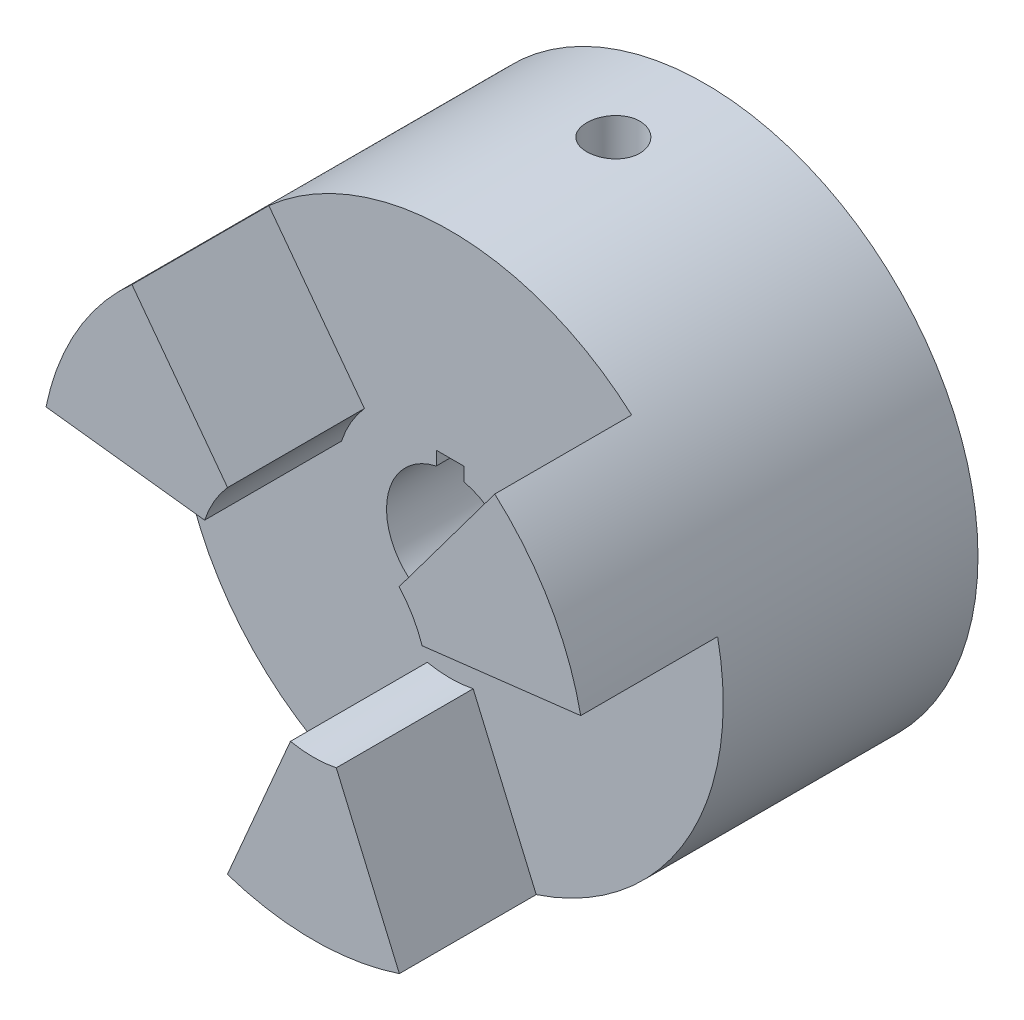
SolidWorks part; units mm, degrees
ref_plane "Płaszczyzna przednia" through (0, 0, 0) normal (0, 0, 1) x (1, 0, 0)
ref_plane "Płaszczyzna górna" through (0, 0, 0) normal (0, 1, 0) x (1, 0, 0)
ref_plane "Płaszczyzna prawa" through (0, 0, 0) normal (1, 0, 0) x (0, 0, -1)
sketch "Szkic1" plane through (0, 0, 0) normal (0, 0, 1) x (1, 0, 0)
  circle A0 centre (0, 0) radius 47.625
  dimension "D1" = 95.25
extrude "Dodanie-wyciągnięcie1" add sketch "Szkic1" along normal blind 44.45
sketch "Szkic2" plane through (0, 0, 44.45) normal (0, 0, 1) x (1, 0, 0)
  line L1 (-2.44, 13.2339) -> (2.44, 13.2339)
  line L2 (-2.44, 13.2339) -> (-2.44, 10.8439)
  line L4 (2.44, 13.2339) -> (2.44, 10.8439)
  arc A0 (-2.44, 10.8439) -> (2.44, 10.8439) centre (0, 0) ccw
  point P8 (0, 13.2339)
  dimension "D1" = 22.23
  dimension "D2" = 4.88
  dimension "D3" = 2.39
extrude "Wytnij-wyciągnięcie1" cut sketch "Szkic2" against normal up to next
sketch "Szkic3" plane through (0, 0, 44.45) normal (0, 0, 1) x (1, 0, 0)
  line L0 (-4, -19.5959) -> (-15, -45.2011)
  line L1 (0, 0) -> (0, -32.7464) construction
  line L2 (4, -19.5959) -> (15, -45.2011)
  circle A0 centre (0, 0) radius 47.625 construction
  circle A1 centre (0, 0) radius 47.625
  circle A2 centre (0, 0) radius 20
  circle M6 centre (0, 0) radius 47.625
  dimension "D1" = 40
  dimension "D2" = 15
  dimension "D3" = 4
extrude "Dodanie-wyciągnięcie2" add sketch "Szkic3" along normal blind 23.88 contours L1 A2 L0 M6 region at (0, -35.9637, 44.45)
pattern_circular "Szyk kołowy1" count 3 over 360 about axis through (0, 0, 44.45) along (0, 0, 1) of "Dodanie-wyciągnięcie2"
ref_plane "Płaszczyzna1" through (0, 47.625, 0) normal (0, 1, 0) x (1, 0, 0)
sketch "Szkic4" plane through (0, 47.625, 0) normal (0, 1, 0) x (1, 0, 0)
  line L0 (-2.44, 0) -> (2.44, 0) construction
  circle A0 centre (0, -16) radius 4.63
  dimension "D1" = 9.26
  dimension "D2" = 16
extrude "Wytnij-wyciągnięcie2" cut sketch "Szkic4" against normal blind 8.64
